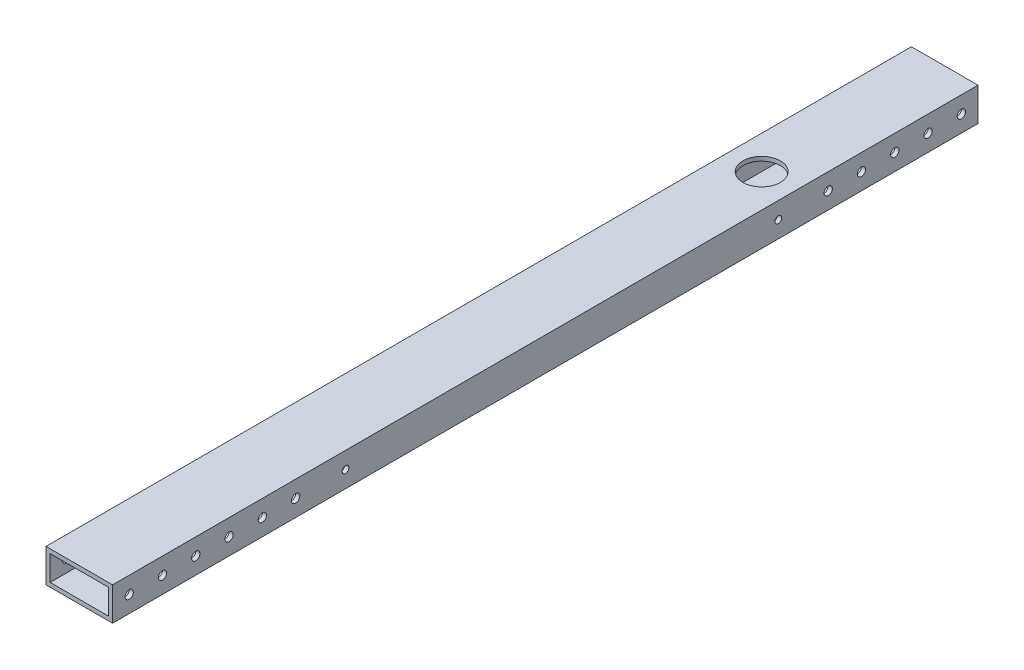
SolidWorks part; units mm, degrees
material "6061 Alloy"
ref_plane "Front Plane" through (0, 0, 0) normal (0, 0, 1) x (1, 0, 0)
ref_plane "Top Plane" through (0, 0, 0) normal (0, 1, 0) x (1, 0, 0)
ref_plane "Right Plane" through (0, 0, 0) normal (1, 0, 0) x (0, 0, -1)
sketch "Sketch1" plane through (0, 0, 0) normal (0, 0, 1) x (1, 0, 0)
  line L0 (-22.225, 9.525) -> (22.225, 9.525)
  line L2 (-25.4, 12.7) -> (25.4, 12.7)
  line L3 (-25.4, 12.7) -> (-25.4, -12.7)
  line L4 (-25.4, -12.7) -> (25.4, -12.7)
  line L5 (25.4, 12.7) -> (25.4, -12.7)
  line L10 (22.225, 9.525) -> (22.225, -9.525)
  line L11 (-22.225, -9.525) -> (22.225, -9.525)
  line L12 (-22.225, 9.525) -> (-22.225, -9.525)
  point P12 (0, 12.7)
  point P14 (25.4, 0)
  dimension "Wall Thickness" = 3.175
  dimension "Outside Width" = 50.8
  dimension "Outside Height" = 25.4
  dimension "Inside Height" = 19.05
  dimension "Inside Width" = 44.45
sketch "Sketch2" plane through (0, 0, 0) normal (1, 0, 0) x (0, 0, -1)
  line L0 (330.2, 0) -> (-330.2, 0)
  point P4 (0, 0)
  point P7 (-330.2, 0)
  point P10 (330.2, 0)
  dimension "Length" = 660.4
sketch "Sketch3" plane through (0, 0, 0) normal (0, 0, 1) x (1, 0, 0)
  line L21 (25.4, 12.7) -> (-25.4, 12.7)
  line L22 (25.4, -12.7) -> (25.4, 12.7)
  line L23 (-25.4, -12.7) -> (25.4, -12.7)
  line L24 (-25.4, 12.7) -> (-25.4, -12.7)
  line L25 (25.4, 12.7) -> (-25.4, 12.7)
  line L26 (25.4, -12.7) -> (25.4, 12.7)
  line L27 (-25.4, -12.7) -> (25.4, -12.7)
  line L28 (-25.4, 12.7) -> (-25.4, -12.7)
  line L29 (22.225, 9.525) -> (-22.225, 9.525)
  line L30 (22.225, -9.525) -> (22.225, 9.525)
  line L31 (-22.225, -9.525) -> (22.225, -9.525)
  line L32 (-22.225, 9.525) -> (-22.225, -9.525)
  line L33 (22.225, 9.525) -> (-22.225, 9.525)
  line L34 (22.225, -9.525) -> (22.225, 9.525)
  line L35 (-22.225, -9.525) -> (22.225, -9.525)
  line L36 (-22.225, 9.525) -> (-22.225, -9.525)
  dimension "D1" = 0
  dimension "D2" = 0
extrude "Boss-Extrude1" add sketch "Sketch3" along normal up to vertex (330.2 mm away) and the other way up to vertex (330.2 mm away) up to point (0, 0, 330.2) other way up to point (0, 0, -330.2)
sketch "Drawing Reference" plane through (0, 0, 0) normal (1, 0, 0) x (0, 0, -1)
  line L0 (-330.2, 0) -> (330.2, 0) construction
  line L1 (0, -12.7) -> (0, 12.7) construction
  line L2 (-330.2, -12.7) -> (330.2, -12.7) construction
  line L5 (-330.2, 12.7) -> (330.2, 12.7) construction
  point P7 (-293.624, 0)
  point P8 (293.624, 0)
  dimension "D1" = 36.576
sketch "Sketch5" plane through (25.4, 0, 0) normal (1, 0, 0) x (0, 0, -1)
  line L2 (-266.7, 0) -> (-241.3, 0)
  line L3 (-241.3, 0) -> (-215.9, 0)
  line L4 (-215.9, 0) -> (-190.5, 0)
  line L5 (-317.5, 0) -> (-330.2, 0)
  line L6 (-330.2, -12.7) -> (-330.2, 12.7) construction
  line L7 (-317.5, 0) -> (-292.1, 0)
  line L8 (-292.1, 0) -> (-266.7, 0)
sketch "Sketch8" plane through (25.4, 0, 0) normal (1, 0, 0) x (0, 0, -1)
  line L0 (330.2, 0) -> (292.1, 0)
  line L1 (330.2, -12.7) -> (330.2, 12.7) construction
  line L2 (292.1, 0) -> (266.7, 0)
  line L3 (266.7, 0) -> (241.3, 0)
  line L4 (241.3, 0) -> (215.9, 0)
  line L5 (330.2, 0) -> (317.5, 0)
hole_wizard "1/4 (0.25) Diameter Hole3" positions "Sketch12" profile "Sketch13" hole size "1/4" standard "ANSI Inch" end condition through all
sketch "Sketch12" plane through (-25.4, 0, 0) normal (-1, 0, 0) x (0, 0, 1)
  point P4 (-317.5, 0)
sketch "Sketch13" plane through (-25.4, 0, -317.5) normal (0, 1, 0) x (0, 0, 1)
  line L0 (0, 0) -> (0, 50.8)
  line L1 (0, 50.8) -> (3.175, 50.8)
  line L2 (3.175, 50.8) -> (3.175, 0)
  line L5 (3.175, 0) -> (0, 0)
  line L11 (0, -6.35) -> (0, 107.95) construction
  dimension "Thru Hole Dia." = 6.35
  dimension "Thru Hole Depth" = 50.8
hole_wizard "1/4 (0.25) Diameter Hole4" positions "Sketch14" profile "Sketch15" hole size "1/4" standard "ANSI Inch" end condition through all
sketch "Sketch14" plane through (-25.4, 0, 0) normal (-1, 0, 0) x (0, 0, 1)
  point P0 (292.1, 0)
  point P3 (317.5, 0)
sketch "Sketch15" plane through (-25.4, 0, 292.1) normal (0, 1, 0) x (0, 0, 1)
  line L0 (0, 0) -> (0, 50.8)
  line L1 (0, 50.8) -> (3.175, 50.8)
  line L2 (3.175, 50.8) -> (3.175, 0)
  line L5 (3.175, 0) -> (0, 0)
  line L11 (0, -6.35) -> (0, 107.95) construction
  dimension "Thru Hole Dia." = 6.35
  dimension "Thru Hole Depth" = 50.8
hole_wizard "1/4 (0.25) Diameter Hole5" positions "Sketch17" profile "Sketch18" hole size "1/4" standard "ANSI Inch" end condition through all
sketch "Sketch17" plane through (25.4, 0, 0) normal (1, 0, 0) x (0, 0, -1)
  point P0 (292.1, 0)
  point P3 (266.7, 0)
sketch "Sketch18" plane through (25.4, 0, -292.1) normal (0, 1, 0) x (0, 0, -1)
  line L0 (0, 0) -> (0, 50.8)
  line L1 (0, 50.8) -> (3.175, 50.8)
  line L2 (3.175, 50.8) -> (3.175, 0)
  line L5 (3.175, 0) -> (0, 0)
  line L11 (0, -6.35) -> (0, 107.95) construction
  dimension "Thru Hole Dia." = 6.35
  dimension "Thru Hole Depth" = 50.8
hole_wizard "1/4 (0.25) Diameter Hole6" positions "Sketch19" profile "Sketch20" hole size "1/4" standard "ANSI Inch" end condition through all
sketch "Sketch19" plane through (25.4, 0, 0) normal (1, 0, 0) x (0, 0, -1)
  point P0 (215.9, 0)
  point P3 (241.3, 0)
sketch "Sketch20" plane through (25.4, 0, -215.9) normal (0, 1, 0) x (0, 0, -1)
  line L0 (0, 0) -> (0, 50.8)
  line L1 (0, 50.8) -> (3.175, 50.8)
  line L2 (3.175, 50.8) -> (3.175, 0)
  line L5 (3.175, 0) -> (0, 0)
  line L11 (0, -6.35) -> (0, 107.95) construction
  dimension "Thru Hole Dia." = 6.35
  dimension "Thru Hole Depth" = 50.8
hole_wizard "1/4 (0.25) Diameter Hole7" positions "Sketch21" profile "Sketch22" hole size "1/4" standard "ANSI Inch" end condition through all
sketch "Sketch21" plane through (25.4, 0, 0) normal (1, 0, 0) x (0, 0, -1)
  point P0 (-190.5, 0)
  point P3 (-215.9, 0)
sketch "Sketch22" plane through (25.4, 0, 190.5) normal (0, 1, 0) x (0, 0, -1)
  line L0 (0, 0) -> (0, 50.8)
  line L1 (0, 50.8) -> (3.175, 50.8)
  line L2 (3.175, 50.8) -> (3.175, 0)
  line L5 (3.175, 0) -> (0, 0)
  line L11 (0, -6.35) -> (0, 107.95) construction
  dimension "Thru Hole Dia." = 6.35
  dimension "Thru Hole Depth" = 50.8
hole_wizard "1/4 (0.25) Diameter Hole8" positions "Sketch23" profile "Sketch24" hole size "1/4" standard "ANSI Inch" end condition through all
sketch "Sketch23" plane through (25.4, 0, 0) normal (1, 0, 0) x (0, 0, -1)
  point P0 (-266.7, 0)
  point P3 (-241.3, 0)
sketch "Sketch24" plane through (25.4, 0, 266.7) normal (0, 1, 0) x (0, 0, -1)
  line L0 (0, 0) -> (0, 50.8)
  line L1 (0, 50.8) -> (3.175, 50.8)
  line L2 (3.175, 50.8) -> (3.175, 0)
  line L5 (3.175, 0) -> (0, 0)
  line L11 (0, -6.35) -> (0, 107.95) construction
  dimension "Thru Hole Dia." = 6.35
  dimension "Thru Hole Depth" = 50.8
sketch "Sketch25" plane through (25.4, 0, 0) normal (1, 0, 0) x (0, 0, -1)
  line L0 (-190.5, 0) -> (-152.4, 0)
  line L1 (215.9, 0) -> (177.8, 0)
hole_wizard "13/64 (0.20313) Diameter Hole1" positions "Sketch26" profile "Sketch27" hole size "13/64" standard "ANSI Inch" end condition through all
sketch "Sketch26" plane through (25.4, 0, 0) normal (1, 0, 0) x (0, 0, -1)
  point P0 (-152.4, 0)
  point P3 (177.8, 0)
sketch "Sketch27" plane through (25.4, 0, 152.4) normal (0, 1, 0) x (0, 0, -1)
  line L0 (0, 0) -> (0, 50.8)
  line L1 (0, 50.8) -> (2.5798, 50.8)
  line L2 (2.5798, 50.8) -> (2.5798, 0)
  line L5 (2.5798, 0) -> (0, 0)
  line L11 (0, -6.35) -> (0, 107.95) construction
  dimension "Thru Hole Dia." = 5.1595
  dimension "Thru Hole Depth" = 50.8
sketch "Sketch28" plane through (-25.4, 0, 0) normal (-1, 0, 0) x (0, 0, 1)
  line L0 (103.1875, 0) -> (77.7875, 0)
  line L1 (-103.1875, 0) -> (-128.5875, 0)
hole_wizard "1/2 (0.5) Diameter Hole1" positions "Sketch29" profile "Sketch30" hole size "1/2" standard "ANSI Inch"
sketch "Sketch29" plane through (-25.4, 0, 0) normal (-1, 0, 0) x (0, 0, 1)
  point P1 (-591.3016, -480.8022)
  point P3 (-103.1875, 0)
  point P6 (77.7875, 0)
  point P9 (103.1875, 0)
  point P13 (-128.5875, 0)
sketch "Sketch30" plane through (-25.4, -480.8022, -591.3016) normal (0, 1, 0) x (0, 0, 1)
  line L0 (0, 0) -> (0, 10.1655)
  line L1 (0, 10.1655) -> (6.35, 6.35)
  line L2 (6.35, 6.35) -> (6.35, 0)
  line L5 (6.35, 0) -> (0, 0)
  line L10 (0, 10.1655) -> (-6.35, 6.35) construction
  line L11 (0, -6.35) -> (0, 107.95) construction
  dimension "Hole Dia." = 12.7
  dimension "Hole Depth" = 6.35
  dimension "Drill Angle" = 118
sketch "Sketch31" plane through (0, -12.7, 0) normal (0, -1, 0) x (1, 0, 0)
  line L0 (-25.4, -190.5081) -> (25.4, -190.5081) construction
  line L1 (-25.4, 330.2) -> (-25.4, -330.2) construction
  line L2 (25.4, 330.2) -> (25.4, -330.2) construction
  line L3 (0, -190.5081) -> (7.7911, -164.2057) construction
  line L5 (-25.4, -154.3741) -> (575.1111, -332.2536) construction
  line L6 (7.7911, -164.2057) -> (10.4085, -164.981) construction
  circle A0 centre (0, -190.5081) radius 14.2875
  dimension "D2" = 28.575
  dimension "D1" = 27.432
extrude "Cut-Extrude1" cut sketch "Sketch31" against normal through all
equation "\"D1@Drawing Reference\"=\"Outside Width@Sketch1\" * 0.72"
